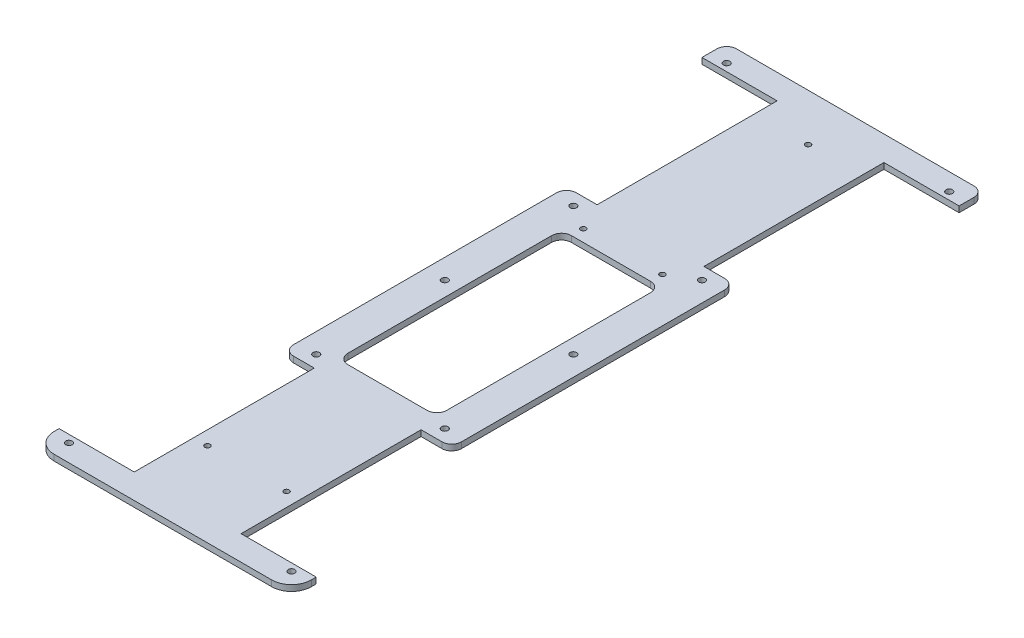
SolidWorks part; units mm, degrees
ref_plane "Front Plane" through (0, 0, 0) normal (0, 0, 1) x (1, 0, 0)
ref_plane "Top Plane" through (0, 0, 0) normal (0, 1, 0) x (1, 0, 0)
ref_plane "Right Plane" through (0, 0, 0) normal (1, 0, 0) x (0, 0, -1)
sketch "Sketch1" plane through (0, 0, 0) normal (0, 1, 0) x (1, 0, 0)
  line L0 (0, 0) -> (130, 0)
  line L1 (0, 0) -> (130, 0) construction
  line L2 (0, 0) -> (0, 350) construction
  line L3 (0, 350) -> (130, 350) construction
  line L4 (130, 0) -> (130, 350) construction
  line L5 (130, 0) -> (130, 12.5)
  line L6 (130, 12.5) -> (92, 12.5)
  line L7 (92, 12.5) -> (92, 103.5)
  line L11 (92, 246.5) -> (92, 337.5)
  line L12 (92, 337.5) -> (130, 337.5)
  line L13 (130, 337.5) -> (130, 350)
  line L14 (130, 350) -> (0, 350)
  line L15 (0, 350) -> (0, 337.5)
  line L16 (0, 337.5) -> (38, 337.5)
  line L17 (38, 337.5) -> (38, 246.5)
  line L21 (38, 103.5) -> (38, 12.5)
  line L22 (38, 12.5) -> (0, 12.5)
  line L23 (0, 12.5) -> (0, 0)
  line L24 (38, 246.5) -> (22.5, 246.5)
  line L25 (22.5, 246.5) -> (22.5, 103.5)
  line L26 (22.5, 103.5) -> (38, 103.5)
  line L27 (92, 246.5) -> (107.5, 246.5)
  line L28 (107.5, 246.5) -> (107.5, 103.5)
  line L29 (107.5, 103.5) -> (92, 103.5)
  dimension "D1" = 130
  dimension "D2" = 350
  dimension "D3" = 38
  dimension "D4" = 91
  dimension "D5" = 22.5
  dimension "D6" = 143
extrude "Boss-Extrude1" add sketch "Sketch1" along normal blind 3
fillet "Fillet1" radius 10 2 edges at (130, 1.5, 0) (0, 1.5, 0)
fillet "Fillet2" radius 5 6 edges at (0, 1.5, -350) (130, 1.5, -350) (107.5, 1.5, -246.5) (107.5, 1.5, -103.5) (22.5, 1.5, -103.5) (22.5, 1.5, -246.5)
sketch "Sketch2" plane through (0, 3, 0) normal (0, 1, 0) x (1, 0, 0)
  line L2 (32.5, 240) -> (32.5, 110) construction
  line L3 (22.5, 175) -> (32.5, 175) construction
  line L4 (22.5, 241.5) -> (22.5, 108.5) construction
  line L5 (65, 350) -> (65, 0) construction
  line L6 (125, 350) -> (5, 350) construction
  line L7 (10, 0) -> (120, 0) construction
  circle A0 centre (32.5, 240) radius 1.65
  circle A1 centre (32.5, 175) radius 1.65
  circle A2 centre (32.5, 110) radius 1.65
  circle A3 centre (97.5, 110) radius 1.65
  circle A4 centre (97.5, 175) radius 1.65
  circle A5 centre (97.5, 240) radius 1.65
  dimension "D3" = 3.3
  dimension "D1" = 10
  dimension "D2" = 130
extrude "Cut-Extrude1" cut sketch "Sketch2" against normal through all
sketch "Sketch3" plane through (0, 3, 0) normal (0, 1, 0) x (1, 0, 0)
  line L0 (0, 12.5) -> (8.75, 12.5) construction
  line L1 (38, 12.5) -> (0, 12.5) construction
  line L2 (8.75, 12.5) -> (8.75, 8.75) construction
  line L3 (65, 0) -> (65, 57.6288) construction
  line L4 (10, 0) -> (120, 0) construction
  circle A0 centre (8.75, 8.75) radius 1.65
  circle A1 centre (121.25, 8.75) radius 1.65
  dimension "D3" = 3.3
  dimension "D1" = 8.75
  dimension "D2" = 3.75
extrude "Cut-Extrude2" cut sketch "Sketch3" against normal through all
sketch "Sketch4" plane through (0, 3, 0) normal (0, 1, 0) x (1, 0, 0)
  line L0 (0, 337.5) -> (8.75, 337.5) construction
  line L1 (0, 337.5) -> (38, 337.5) construction
  line L2 (8.75, 337.5) -> (8.75, 341.25) construction
  line L3 (65, 350) -> (65, 288.2737) construction
  line L4 (125, 350) -> (5, 350) construction
  circle A0 centre (8.75, 341.25) radius 1.65
  circle A1 centre (121.25, 341.25) radius 1.65
  dimension "D3" = 3.3
  dimension "D1" = 8.75
  dimension "D2" = 3.75
extrude "Cut-Extrude3" cut sketch "Sketch4" against normal through all
sketch "Sketch5" plane through (0, 3, 0) normal (0, 1, 0) x (1, 0, 0)
  line L0 (38, 12.5) -> (92, 12.5) construction
  line L1 (65, 12.5) -> (65, 42.5) construction
  line L2 (45, 42.5) -> (85, 42.5) construction
  line L3 (65, 42.5) -> (65, 232.5) construction
  line L4 (45, 232.5) -> (85, 232.5) construction
  line L5 (65, 350) -> (65, 326.15) construction
  line L6 (125, 350) -> (5, 350) construction
  circle A0 centre (45, 42.5) radius 1.35
  circle A1 centre (85, 42.5) radius 1.35
  circle A2 centre (45, 232.5) radius 1.35
  circle A3 centre (85, 232.5) radius 1.35
  circle A4 centre (65, 326.15) radius 1.35
  point P2 (0, 0)
  point P8 (65, 42.5)
  point P14 (65, 232.5)
  dimension "D3" = 2.7
  dimension "D1" = 30
  dimension "D2" = 40
  dimension "D4" = 190
  dimension "D5" = 40
  dimension "D6" = 23.85
extrude "Cut-Extrude4" cut sketch "Sketch5" against normal blind 10
sketch "Sketch6" plane through (0, 3, 0) normal (0, 1, 0) x (1, 0, 0)
  line L0 (38, 246.5) -> (92, 246.5) construction
  line L1 (40, 226.5) -> (90, 226.5)
  line L2 (40, 226.5) -> (40, 113.5)
  line L3 (40, 113.5) -> (90, 113.5)
  line L4 (90, 226.5) -> (90, 113.5)
  line L5 (38, 103.5) -> (92, 103.5) construction
  line L6 (65, 246.5) -> (65, 103.5) construction
  point P13 (65, 113.5)
  point P14 (0, 0)
  point P15 (58.0871, 103.5)
  point P16 (65, 103.5)
  dimension "D1" = 20
  dimension "D2" = 10
  dimension "D3" = 50
extrude "Cut-Extrude5" cut sketch "Sketch6" against normal blind 10
fillet "Fillet4" radius 5 4 edges at (90, 1.5, -113.5) (40, 1.5, -113.5) (90, 1.5, -226.5) (40, 1.5, -226.5)
